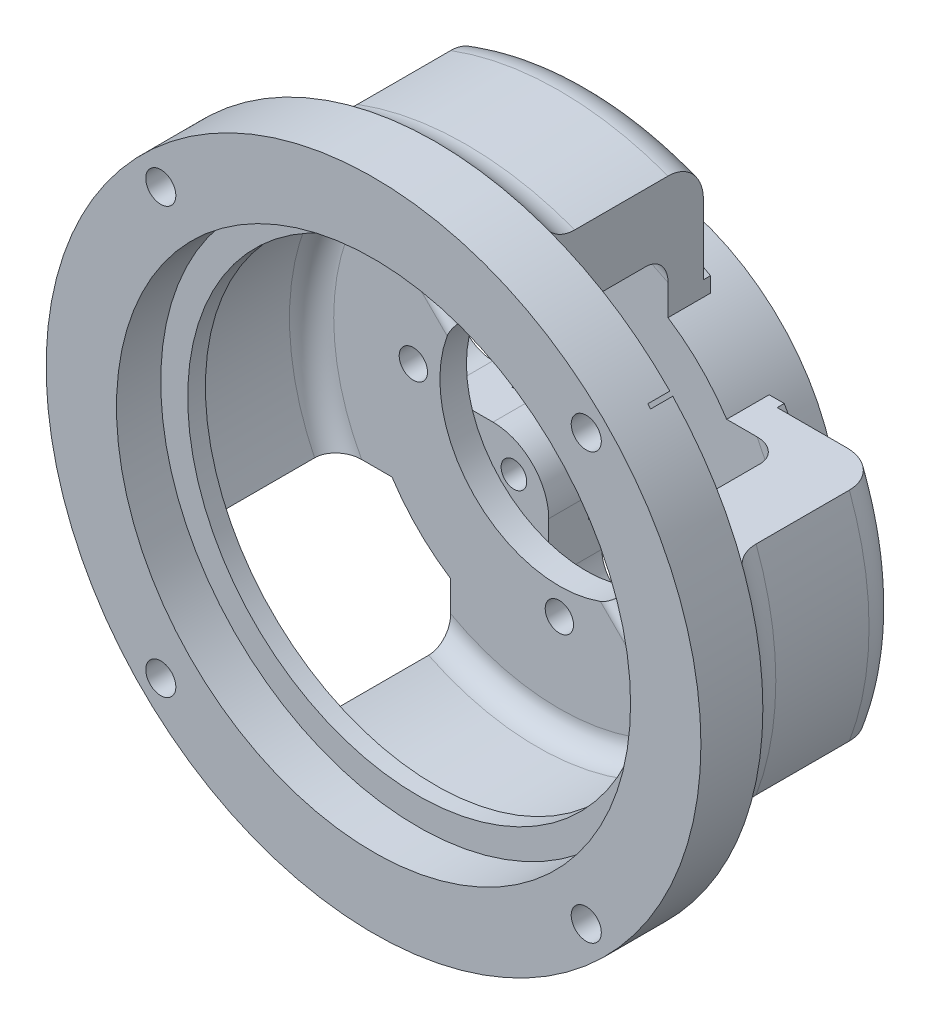
SolidWorks part; units mm, degrees
ref_plane "前视基准面" through (0, 0, 0) normal (0, 0, 1) x (1, 0, 0)
ref_plane "上视基准面" through (0, 0, 0) normal (0, 1, 0) x (1, 0, 0)
ref_plane "右视基准面" through (0, 0, 0) normal (1, 0, 0) x (0, 0, -1)
sketch "草图1" plane through (0, 0, 0) normal (0, 1, 0) x (1, 0, 0)
  line L0 (37, 30.0102) -> (0, 30.0102)
  line L1 (0, 30.0102) -> (0, 24.0102)
  line L2 (0, 24.0102) -> (37, 24.0102)
  line L3 (37, 24.0102) -> (37, 30.0102)
  line L4 (0, 30.0102) -> (0, 24.0102) construction
revolve "旋转1" add sketch "草图1" angle 360 about L4
sketch "草图2" plane through (0, 0, -30.0102) normal (0, 0, -1) x (-1, 0, 0)
  line L24 (-22.4395, -21.2666) -> (-25.6438, -21.2666)
  line L25 (-25.6438, -21.2666) -> (-27.2459, -24.0416)
  line L26 (-20.8373, -24.0416) -> (-22.4395, -21.2666)
  line L27 (-22.4395, -26.8166) -> (-20.8373, -24.0416)
  line L28 (-25.6438, -26.8166) -> (-22.4395, -26.8166)
  line L29 (-27.2459, -24.0416) -> (-25.6438, -26.8166)
  line L75 (-20.8373, -24.0416) -> (-27.2459, -24.0416) construction
  line L76 (-22.4395, -21.2666) -> (-25.6438, -26.8166) construction
  line L77 (-25.6438, -21.2666) -> (-22.4395, -26.8166) construction
  line L78 (0, 0) -> (-24.0416, -24.0416) construction
  line L169 (0, 0) -> (0, -46.6036) construction
  line L170 (-24.0416, 27.2459) -> (-26.8166, 25.6438)
  line L171 (-21.2666, 25.6438) -> (-24.0416, 27.2459)
  line L172 (-21.2666, 22.4395) -> (-21.2666, 25.6438)
  line L173 (-24.0416, 20.8373) -> (-21.2666, 22.4395)
  line L174 (-26.8166, 22.4395) -> (-24.0416, 20.8373)
  line L175 (-26.8166, 25.6438) -> (-26.8166, 22.4395)
  line L176 (27.2459, 24.0416) -> (25.6438, 26.8166)
  line L177 (25.6438, 21.2666) -> (27.2459, 24.0416)
  line L178 (22.4395, 21.2666) -> (25.6438, 21.2666)
  line L179 (20.8373, 24.0416) -> (22.4395, 21.2666)
  line L180 (22.4395, 26.8166) -> (20.8373, 24.0416)
  line L181 (25.6438, 26.8166) -> (22.4395, 26.8166)
  line L182 (24.0416, -27.2459) -> (26.8166, -25.6438)
  line L183 (21.2666, -25.6438) -> (24.0416, -27.2459)
  line L184 (21.2666, -22.4395) -> (21.2666, -25.6438)
  line L185 (24.0416, -20.8373) -> (21.2666, -22.4395)
  line L186 (26.8166, -22.4395) -> (24.0416, -20.8373)
  line L187 (26.8166, -25.6438) -> (26.8166, -22.4395)
  point P24 (0, 0)
  point P41 (0, 0)
  point P74 (0, 0)
  point P165 (0, 0)
  dimension "D1" = 4
  dimension "D2" = 45
extrude "切除-拉伸1" cut sketch "草图2" against normal blind 2.5
hole_wizard "M48 六角头螺栓的柱形沉头孔1" positions "草图15" profile "草图14" counterbore size "M48" standard "ANSI Metric" end condition through all
sketch "草图15" plane through (0, 0, -24.0102) normal (0, 0, 1) x (1, 0, 0)
  point P0 (0, 0)
sketch "草图14" plane through (0, 0, -24.0102) normal (1, 0, 0) x (0, -1, 0)
  line L0 (0, 0) -> (0, 6)
  line L1 (0, 6) -> (26, 6)
  line L3 (26, 6) -> (26, 4)
  line L4 (26, 4) -> (29.05, 4)
  line L5 (29.05, 4) -> (29.05, 0)
  line L7 (29.05, 0) -> (0, 0)
  line L11 (0, -6.35) -> (0, 107.95) construction
  dimension "通孔孔直径" = 52
  dimension "通孔孔深度" = 6
  dimension "柱形沉头孔直径" = 58.1
  dimension "柱形沉头孔深度" = 4
sketch "草图17" plane through (0, 0, -30.0102) normal (0, 0, -1) x (-1, 0, 0)
  line L0 (0, 0) -> (-24.0416, -24.0416) construction
  line L1 (0, 0) -> (0, -49.8277) construction
  circle A0 centre (-24.0416, -24.0416) radius 1.7
  circle A16 centre (-24.0416, 24.0416) radius 1.7
  circle A17 centre (24.0416, 24.0416) radius 1.7
  circle A18 centre (24.0416, -24.0416) radius 1.7
  point P13 (0, 0)
  point P16 (0, 0)
  point P27 (0, 0)
  dimension "D2" = 45
  dimension "D1" = 4
extrude "切除-拉伸2" cut sketch "草图17" against normal blind 6 and the other way through all
sketch "草图18" plane through (0, 0, -30.0102) normal (0, 0, -1) x (-1, 0, 0)
  circle A1 centre (0, 0) radius 35
extrude "凸台-拉伸1" add sketch "草图18" along normal blind 23
sketch "草图19" plane through (0, 0, -30.0102) normal (0, 0, 1) x (1, 0, 0)
  circle A0 centre (0, 0) radius 28
  dimension "D1" = 56
extrude "切除-拉伸3" cut sketch "草图19" against normal blind 14
sketch "草图20" plane through (0, 0, -53.0102) normal (0, 0, -1) x (-1, 0, 0)
  line L0 (0, 0) -> (0, -35) construction
  line L1 (0, 0) -> (-19.0624, -29.3535) construction
  line L2 (0, 0) -> (-29.3535, -19.0624) construction
  line L13 (-18.912, -12.2816) -> (-32.7744, -12.2816)
  line L14 (-12.2816, -32.7744) -> (-12.2816, -18.912) construction
  line L15 (-18.912, -12.2816) -> (-32.7744, -12.2816) construction
  line L16 (-12.2816, 18.912) -> (-12.2816, 32.7744)
  line L17 (-12.2816, -18.912) -> (-12.2816, -32.7744)
  line L18 (-18.912, 12.2816) -> (-32.7744, 12.2816)
  line L19 (18.912, 12.2816) -> (32.7744, 12.2816)
  line L20 (12.2816, 18.912) -> (12.2816, 32.7744)
  line L21 (12.2816, -18.912) -> (12.2816, -32.7744)
  line L22 (18.912, -12.2816) -> (32.7744, -12.2816)
  circle A0 centre (0, 0) radius 35 construction
  arc A1 (-18.912, -12.2816) -> (-12.2816, -18.912) centre (0, 0) ccw
  arc A2 (-29.3535, -19.0624) -> (-19.0624, -29.3535) centre (0, 0) ccw
  arc A19 (-12.2816, 18.912) -> (-18.912, 12.2816) centre (0, 0) ccw
  arc A20 (-19.0624, 29.3535) -> (-29.3535, 19.0624) centre (0, 0) ccw
  arc A21 (18.912, 12.2816) -> (12.2816, 18.912) centre (0, 0) ccw
  arc A22 (29.3535, 19.0624) -> (19.0624, 29.3535) centre (0, 0) ccw
  arc A23 (12.2816, -18.912) -> (18.912, -12.2816) centre (0, 0) ccw
  arc A24 (19.0624, -29.3535) -> (29.3535, -19.0624) centre (0, 0) ccw
  circle A25 centre (0, 0) radius 13.5
  dimension "D1" = 4
  dimension "D2" = 57
  dimension "D3" = 33
extrude "切除-拉伸5" cut sketch "草图20" against normal blind 23
sketch "草图21" plane through (0, 0, -53.0102) normal (0, 0, -1) x (-1, 0, 0)
  line L0 (0, 20.5051) -> (0, -20.6353) construction
  line L1 (-24.3457, 0) -> (20.7655, 0) construction
  line L2 (-4.2, 16.5) -> (-4.2, 10.5)
  line L3 (-10.5, 4.2) -> (-16.5, 4.2)
  line L4 (-20.5, 0.2) -> (-20.5, -0.2)
  line L5 (-16.5, -4.2) -> (-10.5, -4.2)
  line L6 (-4.2, -10.5) -> (-4.2, -16.5)
  line L7 (-0.2, -20.5) -> (0.2, -20.5)
  line L8 (4.2, -16.5) -> (4.2, -10.5)
  line L9 (10.5, -4.2) -> (16.5, -4.2)
  line L10 (20.5, -0.2) -> (20.5, 0.2)
  line L11 (16.5, 4.2) -> (10.5, 4.2)
  line L12 (4.2, 10.5) -> (4.2, 16.5)
  line L13 (0.2, 20.5) -> (-0.2, 20.5)
  arc A0 (-0.2, -20.5) -> (-4.2, -16.5) centre (-0.2, -16.5) cw
  arc A1 (0.2, -20.5) -> (4.2, -16.5) centre (0.2, -16.5) ccw
  arc A2 (20.5, -0.2) -> (16.5, -4.2) centre (16.5, -0.2) cw
  arc A3 (20.5, 0.2) -> (16.5, 4.2) centre (16.5, 0.2) ccw
  arc A4 (4.2, 16.5) -> (0.2, 20.5) centre (0.2, 16.5) ccw
  arc A5 (-0.2, 20.5) -> (-4.2, 16.5) centre (-0.2, 16.5) ccw
  arc A6 (-20.5, -0.2) -> (-16.5, -4.2) centre (-16.5, -0.2) ccw
  arc A7 (-20.5, 0.2) -> (-16.5, 4.2) centre (-16.5, 0.2) cw
  arc A8 (-10.5, 4.2) -> (-4.2, 10.5) centre (-10.5, 10.5) ccw
  arc A9 (4.2, 10.5) -> (10.5, 4.2) centre (10.5, 10.5) ccw
  arc A10 (10.5, -4.2) -> (4.2, -10.5) centre (10.5, -10.5) ccw
  arc A11 (-4.2, -10.5) -> (-10.5, -4.2) centre (-10.5, -10.5) ccw
  point P35 (-4.2, 4.2)
  dimension "D13" = 4
  dimension "D14" = 6.3
  dimension "D1" = 4.2
  dimension "D2" = 20.5
  dimension "D3" = 4.2
  dimension "D4" = 4.2
  dimension "D5" = 4.2
  dimension "D6" = 20.5
  dimension "D7" = 4.2
  dimension "D8" = 4.2
  dimension "D9" = 4.2
  dimension "D10" = 4.2
  dimension "D11" = 20.5
  dimension "D12" = 20.5
extrude "切除-拉伸6" cut sketch "草图21" against normal blind 6
sketch "草图22" plane through (0, 0, -47.0102) normal (0, 0, -1) x (-1, 0, 0)
  line L0 (0, 0) -> (-16.5, 0) construction
  line L1 (0, 0) -> (0, 16.5) construction
  line L2 (0, 0) -> (16.5, 0) construction
  line L3 (0, 0) -> (0, -16.5) construction
  circle A0 centre (-16.5, 0) radius 1.6
  circle A1 centre (0, 16.5) radius 1.6
  circle A2 centre (16.5, 0) radius 1.6
  circle A3 centre (0, -16.5) radius 1.6
  point P9 (0, 0)
  point P17 (0, 0)
extrude "切除-拉伸7" cut sketch "草图22" against normal blind 3
sketch "草图24" plane through (0, 0, -47.0102) normal (0, 0, -1) x (-1, 0, 0)
  line L0 (-12.83, -4.2) -> (-10.5, -4.2)
  line L1 (-4.2, -10.5) -> (-4.2, -12.83)
  line L2 (-12.83, 4.2) -> (-10.5, 4.2)
  line L3 (-4.2, 10.5) -> (-4.2, 12.83)
  line L4 (4.2, 12.83) -> (4.2, 10.5)
  line L5 (10.5, 4.2) -> (12.83, 4.2)
  line L6 (12.83, -4.2) -> (10.5, -4.2)
  line L7 (4.2, -10.5) -> (4.2, -12.83)
  line L8 (0, 0) -> (-8.1317, -8.1317) construction
  circle A0 centre (0, 0) radius 13.5
  arc A1 (4.2, -10.5) -> (10.5, -4.2) centre (10.5, -10.5) cw
  arc A2 (10.5, 4.2) -> (4.2, 10.5) centre (10.5, 10.5) cw
  arc A3 (-4.2, 10.5) -> (-10.5, 4.2) centre (-10.5, 10.5) cw
  arc A4 (-4.2, -10.5) -> (-10.5, -4.2) centre (-10.5, -10.5) ccw
  circle A6 centre (-8.1317, -8.1317) radius 1.45
  circle A7 centre (-8.1317, 8.1317) radius 1.45
  circle A8 centre (8.1317, 8.1317) radius 1.45
  circle A9 centre (8.1317, -8.1317) radius 1.45
  point P33 (-4.2, 4.2)
  point P47 (0, 0)
  dimension "D1" = 6.3
extrude "凸台-拉伸2" add sketch "草图24" along normal blind 4.5
sketch "草图25" plane through (0, 0, -53.0102) normal (0, 0, -1) x (-1, 0, 0)
  circle A0 centre (0, 0) radius 24
  circle A1 centre (0, 0) radius 35
extrude "切除-拉伸8" cut sketch "草图25" against normal blind 5
sketch "草图27" plane through (0, 0, -53.0102) normal (0, 0, -1) x (-1, 0, 0)
  circle A0 centre (0, 0) radius 24
  circle A1 centre (0, 0) radius 22.55
extrude "切除-拉伸9" cut sketch "草图27" against normal blind 4.2
sketch "草图29" plane through (0, 0, -53.0102) normal (0, 0, -1) x (-1, 0, 0)
  line L1 (-9.5, 11.5) -> (9.5, 11.5)
  line L2 (-11.5, 9.5) -> (-11.5, -9.5)
  line L3 (-9.5, -11.5) -> (9.5, -11.5)
  line L4 (11.5, 9.5) -> (11.5, -9.5)
  line L5 (-11.5, 11.5) -> (11.5, -11.5) construction
  line L6 (-11.5, -11.5) -> (11.5, 11.5) construction
  arc A0 (11.5, -9.5) -> (9.5, -11.5) centre (9.5, -9.5) cw
  arc A1 (-9.5, -11.5) -> (-11.5, -9.5) centre (-9.5, -9.5) cw
  arc A2 (11.5, 9.5) -> (9.5, 11.5) centre (9.5, 9.5) ccw
  arc A3 (-9.5, 11.5) -> (-11.5, 9.5) centre (-9.5, 9.5) ccw
  point P0 (0, 0)
  dimension "D1" = 2
extrude "切除-拉伸10" cut sketch "草图29" against normal blind 1.5
fillet "圆角1" radius 4 4 edges at (0, 35, -48.0102) (-35, 0, -48.0102) (0, -35, -48.0102) (35, 0, -48.0102)
fillet "圆角2" radius 2.5 4 edges at (28, 0, -44.0102) (0, -28, -44.0102) (-28, 0, -44.0102) (0, 28, -44.0102)
sketch "草图30" plane through (0, 0, -53.0102) normal (0, 0, -1) x (-1, 0, 0)
  line L0 (0, 0) -> (32.3138, -32.3138) construction
ref_plane "基准面1" through (0, 0, 0) normal (0.7071, -0.7071, 0) x (-0.7071, -0.7071, 0)
sketch "草图31" plane through (0, 0, 0) normal (0.7071, -0.7071, 0) x (-0.7071, -0.7071, 0)
  line L0 (4.6884, 44.0102) -> (4.6884, 48.8102) construction
  line L1 (-4.6884, 44.0102) -> (4.6884, 44.0102)
  line L2 (-4.6884, 44.0102) -> (-4.6884, 46.4102)
  line L3 (-4.6884, 46.4102) -> (4.6884, 46.4102)
  line L4 (4.6884, 44.0102) -> (4.6884, 46.4102)
extrude "切除-拉伸11" cut sketch "草图31" against normal through all both and the other way through all
fillet "圆角3" radius 1 8 edges at (15.5895, -8.9591, -44.0102) (15.5895, -8.9591, -46.4102) (8.9591, -15.5895, -44.0102) (8.9591, -15.5895, -46.4102) (-15.5895, 8.9591, -46.4102) (-8.9591, 15.5895, -44.0102) (-8.9591, 15.5895, -46.4102) (-15.5895, 8.9591, -44.0102)
fillet "圆角4" radius 4 4 edges at (0, -35, -30.0102) (35, 0, -30.0102) (0, 35, -30.0102) (-35, 0, -30.0102)
sketch "草图33" plane through (0, 0, -24.0102) normal (0, 0, 1) x (1, 0, 0)
  circle A0 centre (0, 0) radius 37
  circle A1 centre (0, 0) radius 29.05
  circle A2 centre (-24.0416, -24.0416) radius 1.7
  circle A3 centre (24.0416, -24.0416) radius 1.7
  circle A4 centre (24.0416, 24.0416) radius 1.7
  circle A5 centre (-24.0416, 24.0416) radius 1.7
extrude "凸台-拉伸3" add sketch "草图33" along normal blind 1
